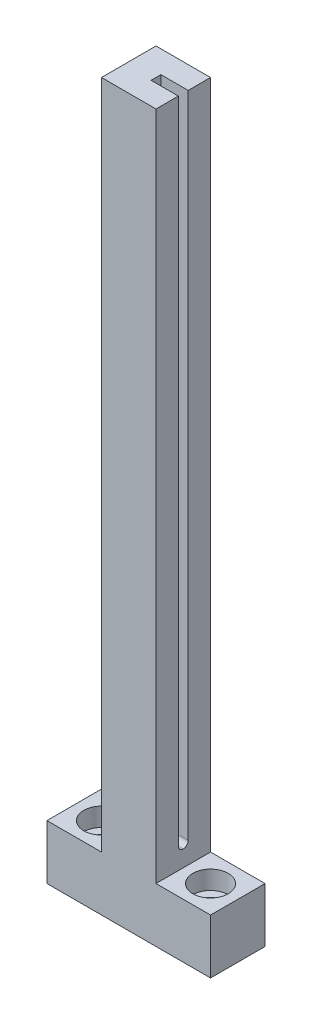
SolidWorks part; units mm, degrees
material "Polyetheretherketone (PEEK)"
ref_plane "Front Plane" through (0, 0, 0) normal (0, 0, 1) x (1, 0, 0)
ref_plane "Top Plane" through (0, 0, 0) normal (0, 1, 0) x (1, 0, 0)
ref_plane "Right Plane" through (0, 0, 0) normal (1, 0, 0) x (0, 0, -1)
sketch "Sketch1" plane through (0, 0, 0) normal (0, 1, 0) x (1, 0, 0)
  line L1 (-5, 5) -> (5, 5)
  line L2 (-5, 5) -> (-5, -5)
  line L3 (-5, -5) -> (5, -5)
  line L4 (5, 5) -> (5, -5)
  line L5 (-5, 5) -> (5, -5) construction
  line L6 (-5, -5) -> (5, 5) construction
  point P0 (0, 0)
  dimension "D1" = 10
  dimension "D2" = 10
extrude "Boss-Extrude1" add sketch "Sketch1" along normal blind 133
sketch "Sketch3" plane through (5, 0, 0) normal (1, 0, 0) x (0, 0, -1)
  line L0 (-5, 133) -> (5, 133) construction
  line L1 (-0.9, 133) -> (0.9, 133)
  line L2 (-0.9, 133) -> (-0.9, 13)
  line L3 (-0.9, 13) -> (0.9, 13)
  line L4 (0.9, 133) -> (0.9, 13)
  line L5 (0, 16.5) -> (0, -16.5) construction
  point P6 (0, 13)
  dimension "D1" = 1.8
  dimension "D2" = 120
extrude "Cut-Extrude1" cut sketch "Sketch3" against normal blind 5
fillet "Fillet1" radius 0.9 2 edges at (2.5, 13, 0.9) (2.5, 13, -0.9)
sketch "Sketch4" plane through (0, 0, 0) normal (1, 0, 0) x (0, 0, -1)
  line L0 (0, 5.5) -> (0, -5.5) construction
  line L1 (-5, 0) -> (5, 0)
  line L2 (-5, 0) -> (-5, 10)
  line L3 (-5, 10) -> (5, 10)
  line L4 (5, 0) -> (5, 10)
  line L5 (-5, 133) -> (-5, 0) construction
  line L6 (-5, 0) -> (5, 0) construction
  point P4 (0, 0)
  dimension "D1" = 10
extrude "Boss-Extrude3" add sketch "Sketch4" along normal mid plane 30
hole_wizard "CBORE for M3 Hex Socket Head Cap Screw1" positions "3DSketch1" profile "Sketch5" counterbore size "M3" standard "ISO" end condition through all
sketch3d "3DSketch1"
  line L0 (15, 10, 5) -> (5, 10, 5) construction
  point P0 (10, 10, 0)
  point P7 (10, 10, 5)
sketch "Sketch5" plane through (10, 10, 0) normal (1, 0, 0) x (0, 0, 1)
  line L0 (0, 0) -> (0, 10)
  line L1 (0, 10) -> (1.7, 10)
  line L3 (1.7, 10) -> (1.7, 3.4)
  line L4 (1.7, 3.4) -> (3.25, 3.4)
  line L5 (3.25, 3.4) -> (3.25, 0)
  line L7 (3.25, 0) -> (0, 0)
  line L11 (0, -6.35) -> (0, 107.95) construction
  dimension "Thru Hole Dia." = 3.4
  dimension "Thru Hole Depth" = 10
  dimension "C'Bore Dia." = 6.5
  dimension "C'Bore Depth" = 3.4
mirror "Mirror1" about plane through (0, 0, 0) normal (1, 0, 0) of "CBORE for M3 Hex Socket Head Cap Screw1"
hole_wizard "Ø1.0mm Dowel Hole1" positions "3DSketch2" profile "Sketch6" hole size "Ø1.0" standard "ISO"
sketch3d "3DSketch2"
  point P0 (0, 0, 0)
sketch "Sketch6" plane through (0, 0, 0) normal (1, 0, 0) x (0, 0, -1)
  line L0 (0, 0) -> (0, 8.3004)
  line L1 (0, 8.3004) -> (0.5, 8)
  line L2 (0.5, 8) -> (0.5, 0)
  line L5 (0.5, 0) -> (0, 0)
  line L10 (0, 8.3004) -> (-0.5, 8) construction
  line L11 (0, -6.35) -> (0, 107.95) construction
  dimension "Hole Dia." = 1
  dimension "Hole Depth" = 8
  dimension "Drill Angle" = 118
